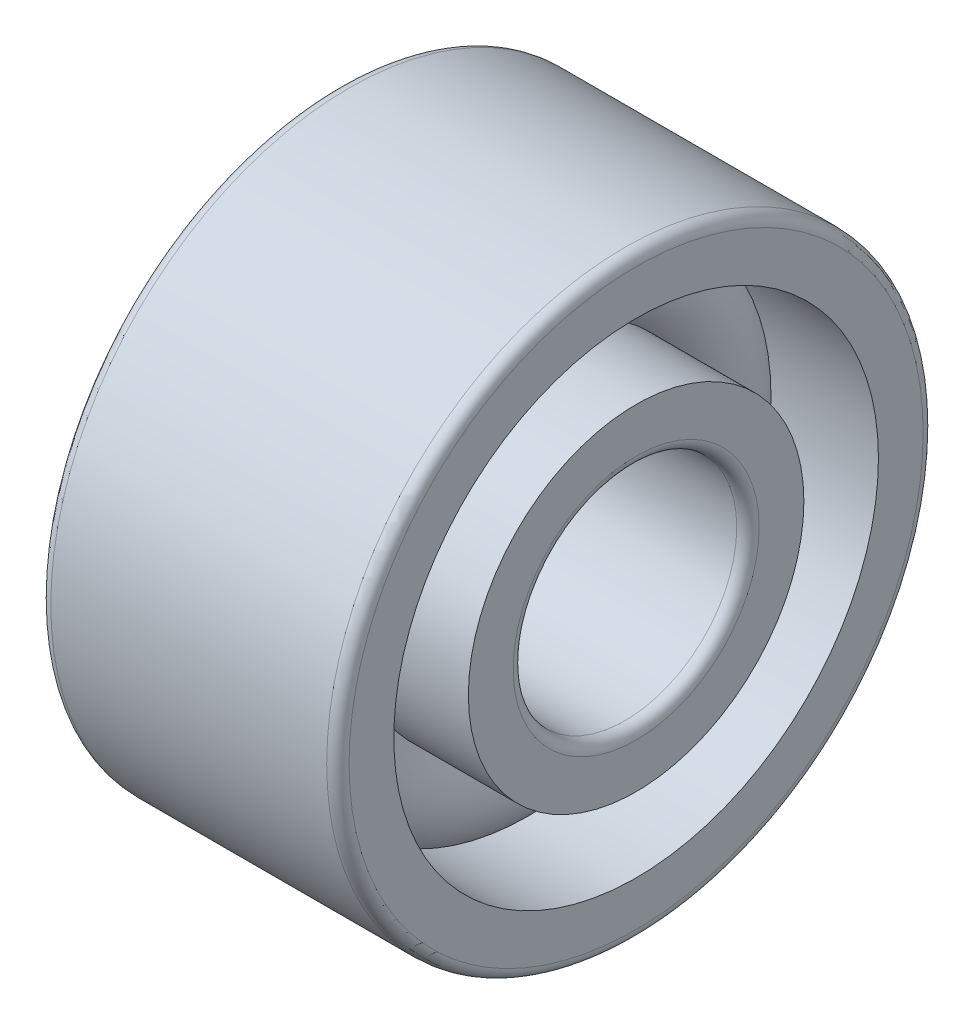
SolidWorks part; units mm, degrees
ref_plane "Plane1" through (0, 0, 0) normal (0, 0, 1) x (1, 0, 0)
ref_plane "Plane2" through (0, 0, 0) normal (0, 1, 0) x (1, 0, 0)
ref_plane "Plane3" through (0, 0, 0) normal (1, 0, 0) x (0, 0, -1)
sketch "Clipboard" plane through (0, 0, 0) normal (0, 0, 1) x (1, 0, 0)
  line L0 (-10, 0) -> (10, 0) construction
  line L1 (0, 0) -> (22.3471, -0.7804)
  line L2 (0, 0) -> (2.7483, 0.096)
  line L3 (0, 0) -> (22.3471, -0.7804)
  line L4 (0, 0) -> (-22.3573, -0.3902)
  dimension "BallCLRad" = 2.75
sketch "CagSpiSke" plane through (0, 0, 0) normal (0, 0, 1) x (1, 0, 0)
  line L0 (0.075, 2.625) -> (0.075, 2.875)
  line L1 (0.075, 2.875) -> (-0.075, 2.875)
  line L2 (-0.075, 2.875) -> (-0.075, 2.625)
  line L3 (-0.075, 2.625) -> (0.075, 2.625)
  line L4 (-20.6375, 0) -> (20.6375, 0) construction
  line L5 (0, 0) -> (0, 23.7692) construction
  dimension "OD" = 5.75
  dimension "ID" = 5.25
revolve "CageSpine" add sketch "CagSpiSke" angle 0.001 about L4 reverse direction yes
ref_axis "Axis1" through (-50, 0, 0) along (1, 0, 0)
sketch "CagBalSke" plane through (0, 0, 0) normal (0, 0, 1) x (1, 0, 0)
  line L0 (-0.825, 2.75) -> (0.825, 2.75)
  line L1 (-1.905, 2.75) -> (1.905, 2.75) construction
  line L2 (-10, 0) -> (10, 0) construction
  line L3 (0, 0) -> (0, 24) construction
  arc A0 (0.825, 2.75) -> (-0.825, 2.75) centre (0, 2.75) cw
  dimension "BallCLRad" = 2.75
revolve "CageBall" [suppressed] add sketch "CagBalSke" angle 360 about L1 reverse direction yes
pattern_circular "CageBalls" [suppressed] count 2 every 180 about axis through (-50, 0, 0) along (1, 0, 0)
sketch "CagTrmODSke" plane through (0, 0, 0) normal (0, 0, 1) x (1, 0, 0)
  line L0 (0.826, 2.875) -> (0.826, 3.576)
  line L1 (0.826, 3.576) -> (-0.826, 3.576)
  line L2 (-0.826, 3.576) -> (-0.826, 2.875)
  line L3 (-0.826, 2.875) -> (0.826, 2.875)
  line L4 (-20.6375, 0) -> (20.6375, 0) construction
  line L5 (0, 0) -> (0, 25) construction
  dimension "Width" = 1.652
  dimension "ID" = 5.75
  dimension "OD" = 7.152
revolve "CageTrimOD" [suppressed] cut sketch "CagTrmODSke" angle 360 about L4 reverse direction yes
sketch "CagTrmIDSke" plane through (0, 0, 0) normal (0, 0, 1) x (1, 0, 0)
  line L0 (0.826, 1.926) -> (0.826, 2.625)
  line L1 (0.826, 2.625) -> (-0.826, 2.625)
  line L2 (-0.826, 2.625) -> (-0.826, 1.926)
  line L3 (-0.826, 1.926) -> (0.826, 1.926)
  line L4 (-20.6375, 0) -> (20.6375, 0) construction
  line L5 (0, 0) -> (0, 25) construction
  dimension "Width" = 1.652
  dimension "ID" = 3.852
  dimension "OD" = 5.25
revolve "CageTrimID" [suppressed] cut sketch "CagTrmIDSke" angle 360 about L4 reverse direction yes
sketch "BalSimSke" plane through (0, 0, 0) normal (0, 0, 1) x (1, 0, 0)
  line L0 (-10, 0) -> (10, 0) construction
  line L1 (-10, 2.75) -> (10, 2.75) construction
  line L2 (0, 0) -> (0, 23) construction
  circle A0 centre (0, 2.75) radius 0.75
  dimension "BallCLRad" = 2.75
  dimension "Ball_diameter" = 1.5
revolve "BallsSimplified" add sketch "BalSimSke" angle 360 about L0
sketch "BalDetSke" plane through (0, 0, 0) normal (0, 0, 1) x (1, 0, 0)
  line L0 (-0.75, 2.75) -> (0.75, 2.75)
  line L1 (-1.905, 2.75) -> (1.905, 2.75) construction
  line L2 (0, 0) -> (0, 25) construction
  arc A0 (0.75, 2.75) -> (-0.75, 2.75) centre (0, 2.75) cw
  dimension "BallCLRad" = 2.75
  dimension "Ball_diameter" = 1.5
revolve "BallDetailed" [suppressed] add sketch "BalDetSke" angle 360 about L1 reverse direction yes
sketch "InnRacSke" plane through (0, 0, 0) normal (0, 0, 1) x (1, 0, 0)
  line L0 (-0.525, 2.25) -> (-2, 2.25)
  line L1 (-2, 2.25) -> (-2, 1.65)
  line L2 (-1.85, 1.5) -> (1.85, 1.5)
  line L3 (2, 1.65) -> (2, 2.25)
  line L4 (2, 2.25) -> (0.525, 2.25)
  line L5 (-20.6375, 0) -> (20.6375, 0) construction
  line L6 (0, 0) -> (0, 30) construction
  arc A0 (-2, 1.65) -> (-1.85, 1.5) centre (-1.85, 1.65) ccw
  arc A1 (1.85, 1.5) -> (2, 1.65) centre (1.85, 1.65) ccw
  arc A2 (0.525, 2.25) -> (-0.525, 2.25) centre (0, 2.75) cw
  dimension "BallCLRad" = 2.75
  dimension "Fillet_radius" = 0.15
  dimension "Ball_diameter" = 1.45
  dimension "ID" = 3
  dimension "OD" = 4.5
  dimension "Width" = 4
revolve "InnerRace" add sketch "InnRacSke" angle 360 about L5 reverse direction yes
sketch "OutRacSke" plane through (0, 0, 0) normal (0, 0, 1) x (1, 0, 0)
  line L0 (-0.525, 3.25) -> (-2, 3.25)
  line L1 (-2, 3.25) -> (-2, 3.85)
  line L2 (-1.85, 4) -> (1.85, 4)
  line L3 (2, 3.85) -> (2, 3.25)
  line L4 (2, 3.25) -> (0.525, 3.25)
  line L5 (-20.6375, 0) -> (20.6375, 0) construction
  line L6 (0, 0) -> (0, 30) construction
  arc A0 (-2, 3.85) -> (-1.85, 4) centre (-1.85, 3.85) cw
  arc A1 (1.85, 4) -> (2, 3.85) centre (1.85, 3.85) cw
  arc A2 (0.525, 3.25) -> (-0.525, 3.25) centre (0, 2.75) ccw
  dimension "BallCLRad" = 2.75
  dimension "Fillet_radius" = 0.15
  dimension "Ball_diameter" = 1.45
  dimension "Width" = 4
revolve "OuterRace" add sketch "OutRacSke" angle 360 about L5 reverse direction yes
pattern_circular "BallsDetailed" [suppressed] count 2 every 180 about axis through (-50, 0, 0) along (1, 0, 0)
equation "\"BallCLRad@Clipboard\" = ( \"OD@OutRacSke\" + \"ID@InnRacSke\" ) / 4"
equation "\"BallCLRad@BalSimSke\" = \"BallCLRad@Clipboard\""
equation "\"BallCLRad@BalDetSke\" = \"BallCLRad@Clipboard\""
equation "\"BallCLRad@InnRacSke\" = \"BallCLRad@Clipboard\""
equation "\"BallCLRad@OutRacSke\" = \"BallCLRad@Clipboard\""
equation "\"Ball_diameter@InnRacSke\" = \"Ball_diameter@BalDetSke\" - 0.05"
equation "\"Ball_diameter@OutRacSke\" = \"Ball_diameter@BalDetSke\" - 0.05"
equation "\"Ball_diameter@BalSimSke\" = \"Ball_diameter@BalDetSke\""
equation "\"Width@OutRacSke\" = \"Width@InnRacSke\""
equation "\"Fillet_radius@OutRacSke\" = \"Fillet_radius@InnRacSke\""
equation "\"Max_count@Clipboard\" = int( 3.14159265 / atn(( \"Ball_diameter@BalDetSke\" / 2) / sqr( \"BallCLRad@Clipboard\"  *  \"BallCLRad@Clipboard\" - ( \"Ball_diameter@BalDetSke\" / 2) *  ( \"Ball_diameter@BalDetSke\" / 2))))"
equation "\"Max_count@Clipboard\" = ((sgn( \"Max_count@Clipboard\" - \"Count@Clipboard\" )-1)*( \"Max_count@Clipboard\" - \"Count@Clipboard\" ))/-2+ \"Count@Clipboard\""
equation "\"Count@BallsDetailed\" = int( \"Show_count@Clipboard\" ) "
equation "\"Count@BallsDetailed\" = ((sgn( \"Count@BallsDetailed\" - \"Max_count@Clipboard\" )-1)*( \"Count@BallsDetailed\" - \"Max_count@Clipboard\" ))/-2+ \"Max_count@Clipboard\""
equation "\"Count@BallsDetailed\" = ((sgn( \"Count@BallsDetailed\" - \"Min_count@Clipboard\" )+1)*( \"Count@BallsDetailed\" - \"Min_count@Clipboard\"))/2 +\"Min_count@Clipboard\""
equation "\"Angle@BallsDetailed\" = 360.0 / \"Max_count@Clipboard\""
equation "\"BallCLRad@CagBalSke\" = \"BallCLRad@Clipboard\""
equation "\"Count@CageBalls\" = \"Count@BallsDetailed\""
equation "\"Angle@CageBalls\" = \"Angle@BallsDetailed\""
equation "\"Angle@CageSpine\" =  \"Angle@CageBalls\" * ( \"Count@CageBalls\" -1 + int( \"Count@CageBalls\" / \"Max_count@Clipboard\" ) )  + 0.001 -  int( \"Count@CageBalls\" / \"Max_count@Clipboard\" ) * 0.001"
equation "\"Angle@CageSpine\" =  \"Angle@CageSpine\" * int( \"Min_count@Clipboard\" / 2) + int(1 / \"Min_count@Clipboard\")  * 0.001"
equation "\"CageWallOD@CagBalSke\" =  \"Ball_diameter@BalDetSke\" * 1.1"
equation "\"Thickness@CagSpiSke\" =  \"Ball_diameter@BalDetSke\" * 0.1"
equation "\"OD@CagTrmODSke\" = \"BallCLRad@Clipboard\" * 2 + \"CageWallOD@CagBalSke\" + 0.002"
equation "\"ID@CagTrmODSke\" = \"BallCLRad@Clipboard\" * 2 + \"Ball_diameter@BalDetSke\" / 6"
equation "\"OD@CagTrmIDSke\" = \"BallCLRad@Clipboard\" * 2 - \"Ball_diameter@BalDetSke\" / 6"
equation "\"ID@CagTrmIDSke\" = \"BallCLRad@Clipboard\" * 2 - \"CageWallOD@CagBalSke\" + 0.002"
equation "\"OD@CagSpiSke\" = \"ID@CagTrmODSke\""
equation "\"ID@CagSpiSke\" = \"OD@CagTrmIDSke\""
equation "\"Width@CagTrmODSke\" = \"CageWallOD@CagBalSke\" + 0.002"
equation "\"Width@CagTrmIDSke\" = \"CageWallOD@CagBalSke\" + 0.002"
